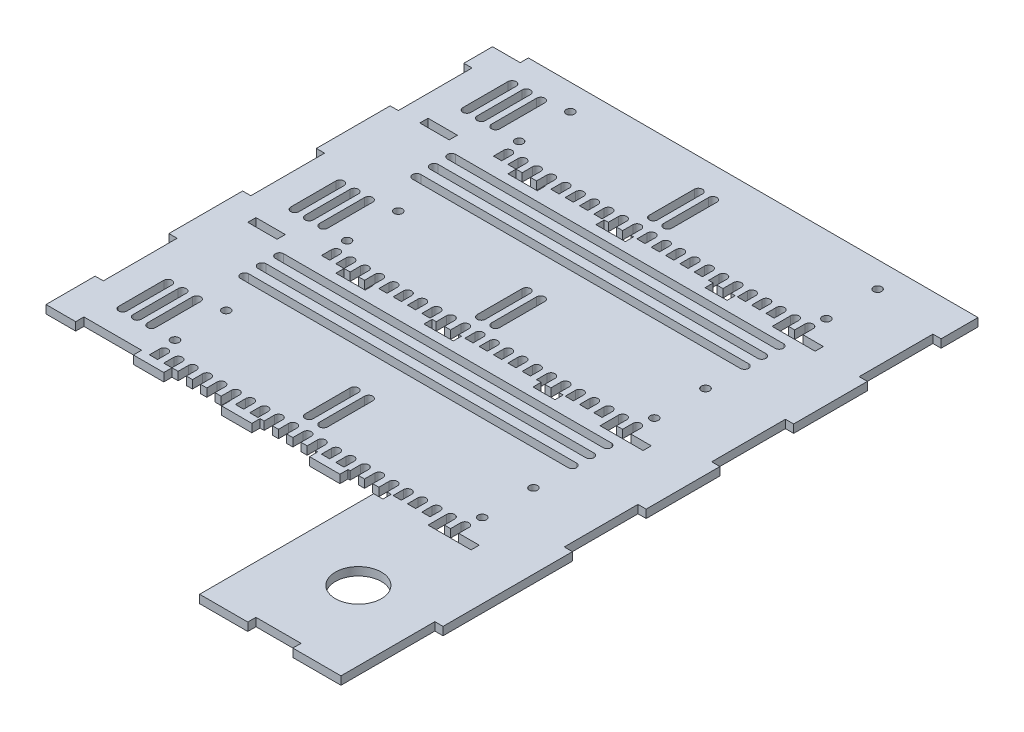
SolidWorks part; units mm, degrees
ref_plane "Front Plane" through (0, 0, 0) normal (0, 0, 1) x (1, 0, 0)
ref_plane "Top Plane" through (0, 0, 0) normal (0, 1, 0) x (1, 0, 0)
ref_plane "Right Plane" through (0, 0, 0) normal (1, 0, 0) x (0, 0, -1)
sketch "Sketch1" plane through (0, 0, 0) normal (0, 1, 0) x (1, 0, 0)
  line L1 (0, 0) -> (233, 0)
  line L2 (0, 0) -> (0, 307)
  line L3 (0, 307) -> (233, 307)
  line L4 (233, 0) -> (233, 307)
  dimension "D1" = 233
  dimension "D2" = 307
extrude "Boss-Extrude1" add sketch "Sketch1" along normal blind 4
sketch "Sketch2" plane through (0, 4, 0) normal (0, 1, 0) x (1, 0, 0)
  line L1 (229, 92.6667) -> (229, 46.3333) construction
  line L2 (0, 0) -> (233, 0) construction
  circle A0 centre (195, 42.5) radius 11.25
  dimension "D1" = 22.5
  dimension "D2" = 42.5
  dimension "D3" = 34
extrude "Cut-Extrude1" cut sketch "Sketch2" against normal through all
sketch "Sketch3" plane through (0, 4, 0) normal (0, 1, 0) x (1, 0, 0)
  line L0 (0, 307) -> (0, 0) construction
  line L1 (0, 85) -> (160, 85)
  line L2 (0, 85) -> (0, 0)
  line L3 (0, 0) -> (160, 0)
  line L4 (160, 85) -> (160, 0)
  line L5 (0, 0) -> (233, 0) construction
  dimension "D1" = 160
extrude "Cut-Extrude2" cut sketch "Sketch3" against normal blind 4
sketch "Sketch5" plane through (0, 0, 0) normal (0, -1, 0) x (1, 0, 0)
  line L0 (233, -307) -> (0, -307) construction
  line L1 (4, -307) -> (13.5, -307)
  line L2 (4, -307) -> (4, -303)
  line L3 (4, -303) -> (13.5, -303)
  line L4 (13.5, -307) -> (13.5, -303)
  line L5 (0, -307) -> (0, -85) construction
  dimension "D3" = 4
  dimension "D2" = 4
  dimension "D1" = 9.5
extrude "Cut-Extrude4" cut sketch "Sketch5" against normal blind 4
sketch "Sketch6" plane through (0, 0, 0) normal (0, -1, 0) x (-1, 0, 0)
  line L0 (-233, 45.83) -> (-233, 0)
  line L5 (-233, 45.83) -> (-229, 45.83)
  line L6 (-229, 45.83) -> (-229, 0)
  line L7 (-233, 0) -> (-229, 0)
  line L8 (-160, 0) -> (-233, 0) construction
  dimension "D4" = 45.83
extrude "Cut-Extrude6" cut sketch "Sketch6" against normal blind 4
sketch "Sketch9" plane through (0, 4, 0) normal (0, 1, 0) x (1, 0, 0)
  line L0 (160, 0) -> (229, 0) construction
  line L1 (183.5, 0) -> (205.5, 0)
  line L2 (183.5, 0) -> (183.5, 4)
  line L3 (183.5, 4) -> (205.5, 4)
  line L4 (205.5, 0) -> (205.5, 4)
  line L6 (160, 0) -> (160, 85) construction
  dimension "D1" = 22
  dimension "D2" = 23.5
  dimension "D3" = 4
extrude "Cut-Extrude7" cut sketch "Sketch9" against normal blind 4
sketch "Sketch10" plane through (0, 4, 0) normal (0, 1, 0) x (1, 0, 0)
  line L0 (0, 85) -> (14.5, 85) construction
  line L1 (160, 85) -> (0, 85) construction
  line L2 (57.5, 85) -> (57.5, 89)
  line L3 (14.5, 85) -> (35.5, 85)
  line L4 (14.5, 85) -> (14.5, 89)
  line L5 (14.5, 89) -> (35.5, 89)
  line L6 (35.5, 85) -> (35.5, 89)
  line L7 (57.5, 85) -> (78.5, 85)
  line L8 (78.5, 85) -> (78.5, 89)
  line L9 (57.5, 89) -> (78.5, 89)
  line L10 (100.5, 85) -> (100.5, 89)
  line L11 (100.5, 85) -> (121.5, 85)
  line L12 (121.5, 85) -> (121.5, 89)
  line L13 (100.5, 89) -> (121.5, 89)
  line L14 (143.5, 85) -> (143.5, 89)
  line L15 (143.5, 85) -> (164.5, 85)
  line L16 (164.5, 85) -> (164.5, 89)
  line L17 (143.5, 89) -> (164.5, 89)
  line L18 (186.5, 85) -> (186.5, 89)
  line L19 (186.5, 85) -> (207.5, 85)
  line L20 (207.5, 85) -> (207.5, 89)
  line L21 (186.5, 89) -> (207.5, 89)
  line L22 (57.5, 169) -> (57.5, 173)
  line L23 (14.5, 169) -> (35.5, 169)
  line L24 (14.5, 169) -> (14.5, 173)
  line L25 (14.5, 173) -> (35.5, 173)
  line L26 (35.5, 169) -> (35.5, 173)
  line L27 (57.5, 169) -> (78.5, 169)
  line L28 (78.5, 169) -> (78.5, 173)
  line L29 (57.5, 173) -> (78.5, 173)
  line L30 (100.5, 169) -> (100.5, 173)
  line L31 (100.5, 169) -> (121.5, 169)
  line L32 (121.5, 169) -> (121.5, 173)
  line L33 (100.5, 173) -> (121.5, 173)
  line L34 (143.5, 169) -> (143.5, 173)
  line L35 (143.5, 169) -> (164.5, 169)
  line L36 (164.5, 169) -> (164.5, 173)
  line L37 (143.5, 173) -> (164.5, 173)
  line L38 (186.5, 169) -> (186.5, 173)
  line L39 (186.5, 169) -> (207.5, 169)
  line L40 (207.5, 169) -> (207.5, 173)
  line L41 (186.5, 173) -> (207.5, 173)
  line L42 (0, 169) -> (14.5, 169) construction
  line L43 (57.5, 253) -> (57.5, 257)
  line L44 (14.5, 253) -> (35.5, 253)
  line L45 (14.5, 253) -> (14.5, 257)
  line L46 (14.5, 257) -> (35.5, 257)
  line L47 (35.5, 253) -> (35.5, 257)
  line L48 (57.5, 253) -> (78.5, 253)
  line L49 (78.5, 253) -> (78.5, 257)
  line L50 (57.5, 257) -> (78.5, 257)
  line L51 (100.5, 253) -> (100.5, 257)
  line L52 (100.5, 253) -> (121.5, 253)
  line L53 (121.5, 253) -> (121.5, 257)
  line L54 (100.5, 257) -> (121.5, 257)
  line L55 (143.5, 253) -> (143.5, 257)
  line L56 (143.5, 253) -> (164.5, 253)
  line L57 (164.5, 253) -> (164.5, 257)
  line L58 (143.5, 257) -> (164.5, 257)
  line L59 (186.5, 253) -> (186.5, 257)
  line L60 (186.5, 253) -> (207.5, 253)
  line L61 (207.5, 253) -> (207.5, 257)
  line L62 (186.5, 257) -> (207.5, 257)
  line L63 (0, 253) -> (14.5, 253) construction
  dimension "D1" = 14.5
  dimension "D2" = 4
  dimension "D3" = 21
  dimension "D4" = 5
extrude "Cut-Extrude8" cut sketch "Sketch10" against normal blind 4
sketch "Sketch11" plane through (0, 4, 0) normal (0, 1, 0) x (1, 0, 0)
  line L0 (57.5, 85) -> (35.5, 85) construction
  line L1 (42.667, 85) -> (28.8337, 85)
  line L2 (42.667, 85) -> (42.667, 89)
  line L3 (42.667, 89) -> (28.8337, 89)
  line L4 (28.8337, 85) -> (28.8337, 89)
  line L5 (35.5, 89) -> (14.5, 89) construction
  line L6 (57.5, 89) -> (57.5, 85) construction
  line L7 (85.667, 85) -> (85.667, 89)
  line L8 (85.667, 85) -> (71.8337, 85)
  line L9 (71.8337, 85) -> (71.8337, 89)
  line L10 (85.667, 89) -> (71.8337, 89)
  line L11 (128.667, 85) -> (128.667, 89)
  line L12 (128.667, 85) -> (114.8337, 85)
  line L13 (114.8337, 85) -> (114.8337, 89)
  line L14 (128.667, 89) -> (114.8337, 89)
  dimension "D1" = 13.8333
  dimension "D2" = 14.833
  dimension "D3" = 3
extrude "Cut-Extrude9" cut sketch "Sketch11" against normal blind 4
sketch "Sketch14" plane through (0, 4, 0) normal (0, 1, 0) x (1, 0, 0)
  line L0 (14.5, 169) -> (35.5, 169) construction
  line L1 (35.5, 173) -> (28.83, 173)
  line L2 (35.5, 173) -> (35.5, 169)
  line L3 (35.5, 169) -> (28.83, 169)
  line L4 (28.83, 173) -> (28.83, 169)
  line L5 (57.5, 169) -> (78.5, 169) construction
  line L6 (78.5, 173) -> (71.83, 173)
  line L7 (78.5, 173) -> (78.5, 169)
  line L8 (78.5, 169) -> (71.83, 169)
  line L9 (71.83, 173) -> (71.83, 169)
  line L10 (100.5, 169) -> (121.5, 169) construction
  line L11 (121.5, 173) -> (114.83, 173)
  line L12 (121.5, 173) -> (121.5, 169)
  line L13 (121.5, 169) -> (114.83, 169)
  line L14 (114.83, 173) -> (114.83, 169)
  line L15 (143.5, 169) -> (164.5, 169) construction
  line L16 (143.5, 173) -> (153.75, 173)
  line L17 (143.5, 173) -> (143.5, 169)
  line L18 (143.5, 169) -> (153.75, 169)
  line L19 (153.75, 173) -> (153.75, 169)
  line L20 (143.5, 257) -> (143.5, 253)
  line L21 (143.5, 257) -> (153.75, 257)
  line L22 (153.75, 257) -> (153.75, 253)
  line L23 (143.5, 253) -> (153.75, 253)
  line L24 (35.5, 257) -> (35.5, 253)
  line L25 (35.5, 257) -> (28.83, 257)
  line L26 (28.83, 257) -> (28.83, 253)
  line L27 (35.5, 253) -> (28.83, 253)
  line L28 (78.5, 257) -> (78.5, 253)
  line L29 (78.5, 257) -> (71.83, 257)
  line L30 (71.83, 257) -> (71.83, 253)
  line L31 (78.5, 253) -> (71.83, 253)
  line L32 (121.5, 257) -> (121.5, 253)
  line L33 (121.5, 257) -> (114.83, 257)
  line L34 (114.83, 257) -> (114.83, 253)
  line L35 (121.5, 253) -> (114.83, 253)
extrude "Boss-Extrude2" add sketch "Sketch14" against normal blind 4
sketch "Sketch15" plane through (0, 4, 0) normal (0, 1, 0) x (1, 0, 0)
  line L0 (0, 307) -> (0, 85) construction
  line L1 (0, 289) -> (4, 289)
  line L2 (0, 289) -> (0, 253)
  line L3 (0, 253) -> (4, 253)
  line L4 (4, 289) -> (4, 253)
  line L5 (4, 307) -> (0, 307) construction
  line L26 (0, 217) -> (0, 181)
  line L27 (0, 217) -> (4, 217)
  line L28 (4, 217) -> (4, 181)
  line L29 (0, 181) -> (4, 181)
  line L30 (0, 145) -> (0, 109)
  line L31 (0, 145) -> (4, 145)
  line L32 (4, 145) -> (4, 109)
  line L33 (0, 109) -> (4, 109)
  dimension "D1" = 4
  dimension "D2" = 36
  dimension "D3" = 18
extrude "Cut-Extrude11" cut sketch "Sketch15" against normal blind 4
sketch "Sketch16" plane through (0, 4, 0) normal (0, 1, 0) x (1, 0, 0)
  line L0 (233, 45.83) -> (233, 307) construction
  line L1 (233, 289) -> (229, 289)
  line L2 (233, 289) -> (233, 253)
  line L3 (233, 253) -> (229, 253)
  line L4 (229, 289) -> (229, 253)
  line L5 (233, 307) -> (13.5, 307) construction
  line L6 (233, 217) -> (233, 181)
  line L7 (233, 217) -> (229, 217)
  line L8 (229, 217) -> (229, 181)
  line L9 (233, 181) -> (229, 181)
  line L10 (233, 145) -> (233, 109)
  line L11 (233, 145) -> (229, 145)
  line L12 (229, 145) -> (229, 109)
  line L13 (233, 109) -> (229, 109)
  dimension "D1" = 18
  dimension "D2" = 36
  dimension "D3" = 4
extrude "Cut-Extrude12" cut sketch "Sketch16" against normal blind 4
sketch "Sketch12" plane through (0, 4, 0) normal (0, 1, 0) x (1, 0, 0)
  line L0 (20.5, 292) -> (20.5, 270) construction
  line L1 (22.5, 292) -> (22.5, 270)
  line L2 (18.5, 292) -> (18.5, 270)
  line L3 (13.5, 307) -> (13.5, 303) construction
  line L4 (13.5, 303) -> (4, 303) construction
  line L11 (111.5, 292) -> (111.5, 270) construction
  line L12 (113.5, 292) -> (113.5, 270)
  line L13 (109.5, 292) -> (109.5, 270)
  line L14 (118.5, 292) -> (118.5, 270) construction
  line L15 (120.5, 292) -> (120.5, 270)
  line L16 (116.5, 292) -> (116.5, 270)
  line L17 (109.5, 256.97) -> (113.5, 256.97)
  line L18 (25.5, 292) -> (25.5, 270)
  line L21 (29.5, 292) -> (29.5, 270)
  line L22 (27.5, 292) -> (27.5, 270) construction
  line L23 (34.5, 292) -> (34.5, 270) construction
  line L24 (36.5, 292) -> (36.5, 270)
  line L25 (32.5, 292) -> (32.5, 270)
  line L26 (102.5, 262) -> (102.5, 256.97)
  line L27 (111.5, 262) -> (111.5, 257) construction
  line L28 (114.83, 257) -> (100.5, 257) construction
  line L29 (113.5, 262) -> (113.5, 256.97)
  line L30 (109.5, 262) -> (109.5, 256.97)
  line L31 (102.5, 256.97) -> (106.5, 256.97)
  line L32 (106.5, 262) -> (106.5, 256.97)
  line L33 (95.5, 262) -> (95.5, 256.97)
  line L34 (95.5, 256.97) -> (99.5, 256.97)
  line L35 (99.5, 262) -> (99.5, 256.97)
  line L36 (88.5, 262) -> (88.5, 256.97)
  line L37 (88.5, 256.97) -> (92.5, 256.97)
  line L38 (92.5, 262) -> (92.5, 256.97)
  line L39 (81.5, 262) -> (81.5, 256.97)
  line L40 (81.5, 256.97) -> (85.5, 256.97)
  line L41 (85.5, 262) -> (85.5, 256.97)
  line L42 (74.5, 262) -> (74.5, 256.97)
  line L43 (74.5, 256.97) -> (78.5, 256.97)
  line L44 (78.5, 262) -> (78.5, 256.97)
  line L45 (67.5, 262) -> (67.5, 256.97)
  line L46 (67.5, 256.97) -> (71.5, 256.97)
  line L47 (71.5, 262) -> (71.5, 256.97)
  line L48 (60.5, 262) -> (60.5, 256.97)
  line L49 (60.5, 256.97) -> (64.5, 256.97)
  line L50 (64.5, 262) -> (64.5, 256.97)
  line L51 (53.5, 262) -> (53.5, 256.97)
  line L52 (53.5, 256.97) -> (57.5, 256.97)
  line L53 (57.5, 262) -> (57.5, 256.97)
  line L54 (116.5, 262) -> (116.5, 256.97)
  line L55 (116.5, 256.97) -> (120.5, 256.97)
  line L56 (120.5, 262) -> (120.5, 256.97)
  line L57 (123.5, 262) -> (123.5, 256.97)
  line L58 (123.5, 256.97) -> (127.5, 256.97)
  line L59 (127.5, 262) -> (127.5, 256.97)
  line L60 (130.5, 262) -> (130.5, 256.97)
  line L61 (130.5, 256.97) -> (134.5, 256.97)
  line L62 (134.5, 262) -> (134.5, 256.97)
  line L63 (137.5, 262) -> (137.5, 256.97)
  line L64 (137.5, 256.97) -> (141.5, 256.97)
  line L65 (141.5, 262) -> (141.5, 256.97)
  line L66 (144.5, 262) -> (144.5, 256.97)
  line L67 (144.5, 256.97) -> (148.5, 256.97)
  line L68 (148.5, 262) -> (148.5, 256.97)
  line L69 (151.5, 262) -> (151.5, 256.97)
  line L70 (151.5, 256.97) -> (155.5, 256.97)
  line L71 (155.5, 262) -> (155.5, 256.97)
  line L72 (158.5, 262) -> (158.5, 256.97)
  line L73 (158.5, 256.97) -> (162.5, 256.97)
  line L74 (162.5, 262) -> (162.5, 256.97)
  line L75 (165.5, 262) -> (165.5, 256.97)
  line L76 (165.5, 256.97) -> (169.5, 256.97)
  line L77 (169.5, 262) -> (169.5, 256.97)
  line L78 (172.5, 262) -> (172.5, 256.97)
  line L79 (172.5, 256.97) -> (176.5, 256.97)
  line L80 (176.5, 262) -> (176.5, 256.97)
  line L81 (179.5, 262) -> (179.5, 256.97)
  line L82 (179.5, 256.97) -> (183.5, 256.97)
  line L83 (183.5, 262) -> (183.5, 256.97)
  line L84 (186.5, 262) -> (186.5, 256.97)
  line L85 (186.5, 256.97) -> (190.5, 256.97)
  line L86 (190.5, 262) -> (190.5, 256.97)
  line L87 (46.5, 262) -> (46.5, 256.97)
  line L88 (46.5, 256.97) -> (50.5, 256.97)
  line L89 (50.5, 262) -> (50.5, 256.97)
  line L90 (193.5, 262) -> (193.5, 256.97)
  line L91 (193.5, 256.97) -> (197.5, 256.97)
  line L92 (197.5, 262) -> (197.5, 256.97)
  arc A0 (22.5, 292) -> (18.5, 292) centre (20.5, 292) ccw
  arc A1 (18.5, 270) -> (22.5, 270) centre (20.5, 270) ccw
  arc A6 (113.5, 292) -> (109.5, 292) centre (111.5, 292) ccw
  arc A7 (109.5, 270) -> (113.5, 270) centre (111.5, 270) ccw
  arc A8 (120.5, 292) -> (116.5, 292) centre (118.5, 292) ccw
  arc A9 (116.5, 270) -> (120.5, 270) centre (118.5, 270) ccw
  arc A14 (29.5, 292) -> (25.5, 292) centre (27.5, 292) ccw
  arc A15 (25.5, 270) -> (29.5, 270) centre (27.5, 270) ccw
  arc A16 (36.5, 292) -> (32.5, 292) centre (34.5, 292) ccw
  arc A17 (32.5, 270) -> (36.5, 270) centre (34.5, 270) ccw
  arc A18 (113.5, 262) -> (109.5, 262) centre (111.5, 262) ccw
  arc A20 (106.5, 262) -> (102.5, 262) centre (104.5, 262) ccw
  arc A21 (99.5, 262) -> (95.5, 262) centre (97.5, 262) ccw
  arc A22 (92.5, 262) -> (88.5, 262) centre (90.5, 262) ccw
  arc A23 (85.5, 262) -> (81.5, 262) centre (83.5, 262) ccw
  arc A24 (78.5, 262) -> (74.5, 262) centre (76.5, 262) ccw
  arc A25 (71.5, 262) -> (67.5, 262) centre (69.5, 262) ccw
  arc A26 (64.5, 262) -> (60.5, 262) centre (62.5, 262) ccw
  arc A27 (57.5, 262) -> (53.5, 262) centre (55.5, 262) ccw
  arc A28 (120.5, 262) -> (116.5, 262) centre (118.5, 262) ccw
  arc A29 (127.5, 262) -> (123.5, 262) centre (125.5, 262) ccw
  arc A30 (134.5, 262) -> (130.5, 262) centre (132.5, 262) ccw
  arc A31 (141.5, 262) -> (137.5, 262) centre (139.5, 262) ccw
  arc A32 (148.5, 262) -> (144.5, 262) centre (146.5, 262) ccw
  arc A33 (155.5, 262) -> (151.5, 262) centre (153.5, 262) ccw
  arc A34 (162.5, 262) -> (158.5, 262) centre (160.5, 262) ccw
  arc A35 (169.5, 262) -> (165.5, 262) centre (167.5, 262) ccw
  arc A36 (176.5, 262) -> (172.5, 262) centre (174.5, 262) ccw
  arc A37 (183.5, 262) -> (179.5, 262) centre (181.5, 262) ccw
  arc A38 (190.5, 262) -> (186.5, 262) centre (188.5, 262) ccw
  arc A39 (50.5, 262) -> (46.5, 262) centre (48.5, 262) ccw
  arc A40 (197.5, 262) -> (193.5, 262) centre (195.5, 262) ccw
  point P2 (20.5, 281)
  point P14 (111.5, 258.5)
  point P16 (27.5, 281)
  point P23 (34.5, 281)
  point P28 (111.5, 281)
  point P35 (118.5, 281)
  dimension "D12" = 8
  dimension "D2" = 4
  dimension "D3" = 7
  dimension "D4" = 11
  dimension "D6" = 2
  dimension "D8" = 4
  dimension "D10" = 7
  dimension "D11" = 73
  dimension "D15" = 5.03
  dimension "D17" = 22
  dimension "D7" = 2
  dimension "D9" = 2
  dimension "D5" = 2
  dimension "D13" = 9
  dimension "D14" = 12
  dimension "D16" = 2
  dimension "D18" = 2
extrude "Cut-Extrude10" cut sketch "Sketch12" against normal blind 4
pattern_linear "LPattern1" count 3 spacing 84 along (0, 0, 1) of "Cut-Extrude10"
sketch "Sketch17" plane through (0, 4, 0) normal (0, 1, 0) x (1, 0, 0)
  line L0 (196.5, 162.47) -> (36.5, 162.47) construction
  line L1 (196.5, 160.47) -> (36.5, 160.47)
  line L2 (196.5, 164.47) -> (36.5, 164.47)
  line L3 (179.5, 172.97) -> (183.5, 172.97) construction
  line L4 (0, 181) -> (0, 145) construction
  line L5 (196.5, 155.97) -> (36.5, 155.97)
  line L6 (196.5, 151.97) -> (36.5, 151.97)
  line L7 (196.5, 153.97) -> (36.5, 153.97) construction
  line L8 (196.5, 147.47) -> (36.5, 147.47)
  line L9 (196.5, 143.47) -> (36.5, 143.47)
  line L10 (196.5, 145.47) -> (36.5, 145.47) construction
  arc A0 (196.5, 160.47) -> (196.5, 164.47) centre (196.5, 162.47) ccw
  arc A1 (36.5, 164.47) -> (36.5, 160.47) centre (36.5, 162.47) ccw
  arc A2 (196.5, 151.97) -> (196.5, 155.97) centre (196.5, 153.97) ccw
  arc A3 (36.5, 155.97) -> (36.5, 151.97) centre (36.5, 153.97) ccw
  arc A4 (196.5, 143.47) -> (196.5, 147.47) centre (196.5, 145.47) ccw
  arc A5 (36.5, 147.47) -> (36.5, 143.47) centre (36.5, 145.47) ccw
  point P2 (116.5, 162.47)
  point P15 (116.5, 153.97)
  point P22 (116.5, 145.47)
  dimension "D1" = 8.5
  dimension "D2" = 4
  dimension "D3" = 160
  dimension "D4" = 116.5
extrude "Cut-Extrude13" cut sketch "Sketch17" against normal blind 4
pattern_linear "LPattern2" count 2 spacing 84 along (0, 0, -1) of "Cut-Extrude13"
sketch "Sketch18" plane through (0, 4, 0) normal (0, 1, 0) x (1, 0, 0)
  line L0 (229, 289) -> (229, 253) construction
  line L1 (179.5, 256.97) -> (183.5, 256.97) construction
  circle A0 centre (196.5, 269.47) radius 2
  circle A1 centre (46.5, 269.47) radius 2
  circle A2 centre (46.5, 294.47) radius 2
  circle A3 centre (196.5, 294.47) radius 2
  dimension "D2" = 4
  dimension "D1" = 32.5
  dimension "D3" = 12.5
  dimension "D4" = 2
extrude "Cut-Extrude14" cut sketch "Sketch18" against normal blind 4
pattern_linear "LPattern3" count 3 spacing 84 along (0, 0, 1) of "Cut-Extrude14"
sketch "Sketch19" plane through (0, 0, -307) normal (0, 0, -1) x (-1, 0, 0)
  line L4 (0, 4) -> (-4, 4)
  line L5 (-4, 4) -> (-4, 0)
  line L6 (-4, 0) -> (0, 0)
  line L7 (0, 0) -> (0, 4)
  line L8 (0, 4) -> (-4, 4)
  line L9 (-4, 4) -> (-4, 0)
  line L10 (-4, 0) -> (0, 0)
  line L11 (0, 0) -> (0, 4)
  dimension "D1" = 0
extrude "Cut-Extrude15" cut sketch "Sketch19" against normal blind 4
equation "\"Dikte\"= 4"
equation "\"D1@Sketch1\"=\"Dikte\"*2+225"
equation "\"D2@Sketch1\"=135+\"Dikte\"+2*34+2*50"
equation "\"Tolerantie\"= 0.5"
equation "\"D1@Sketch9\"=23-2*\"Tolerantie\""
equation "\"D2@Sketch9\"=23+\"Tolerantie\""
equation "\"D1@Sketch10\"=14+\"Tolerantie\""
equation "\"D3@Sketch10\"=21.5-\"Tolerantie\""
equation "\"D1@Sketch11\"=14.33333-\"Tolerantie\""
equation "\"D2@Sketch11\"=14.333+\"Tolerantie\""
equation "\"D1@Sketch5\"=10-\"Tolerantie\""
